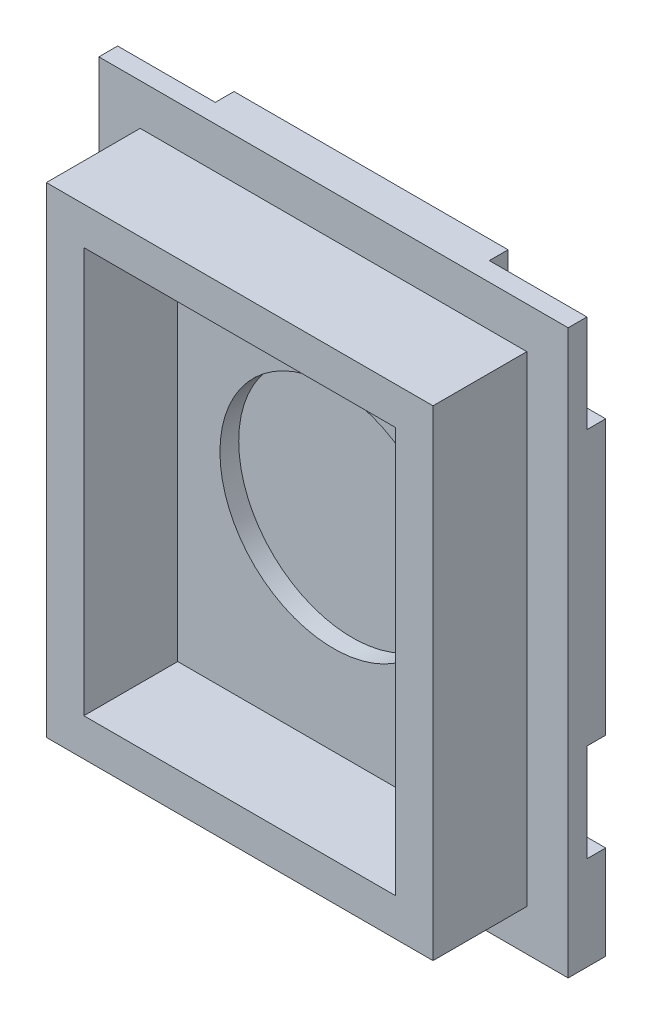
SolidWorks part; units mm, degrees
ref_plane "正面" through (0, 0, 0) normal (0, 0, 1) x (1, 0, 0)
ref_plane "平面" through (0, 0, 0) normal (0, 1, 0) x (1, 0, 0)
ref_plane "右側面" through (0, 0, 0) normal (1, 0, 0) x (0, 0, -1)
sketch "ｽｹｯﾁ1" plane through (0, 0, 0) normal (0, 0, 1) x (1, 0, 0)
  line L1 (-36.7373, 39.7071) -> (-11.7373, 39.7071)
  line L2 (-36.7373, 39.7071) -> (-36.7373, 9.7071)
  line L3 (-36.7373, 9.7071) -> (-11.7373, 9.7071)
  line L4 (-11.7373, 39.7071) -> (-11.7373, 9.7071)
  dimension "D3" = 25
  dimension "D4" = 30
extrude "ﾎﾞｽ - 押し出し1" add sketch "ｽｹｯﾁ1" along normal blind 2
sketch "ｽｹｯﾁ2" plane through (0, 0, 2) normal (0, 0, 1) x (1, 0, 0)
  line L0 (-11.7373, 39.7071) -> (-36.7373, 39.7071) construction
  line L1 (-13.9373, 37.5071) -> (-34.5373, 37.5071)
  line L2 (-13.9373, 37.5071) -> (-13.9373, 11.9071)
  line L3 (-13.9373, 11.9071) -> (-34.5373, 11.9071)
  line L4 (-34.5373, 37.5071) -> (-34.5373, 11.9071)
  line L5 (-36.7373, 9.7071) -> (-11.7373, 9.7071) construction
  line L6 (-36.7373, 39.7071) -> (-36.7373, 9.7071) construction
  line L7 (-11.7373, 9.7071) -> (-11.7373, 39.7071) construction
  dimension "D2" = 2.2
  dimension "D3" = 2.2
  dimension "D4" = 2.2
  dimension "D5" = 2.2
extrude "ﾎﾞｽ - 押し出し2" add sketch "ｽｹｯﾁ2" along normal blind 5
sketch "ｽｹｯﾁ3" plane through (0, 0, 7) normal (0, 0, 1) x (1, 0, 0)
  line L0 (-13.9373, 37.5071) -> (-34.5373, 37.5071) construction
  line L1 (-32.5373, 13.9071) -> (-15.9373, 13.9071)
  line L2 (-32.5373, 13.9071) -> (-32.5373, 35.5071)
  line L3 (-32.5373, 35.5071) -> (-15.9373, 35.5071)
  line L4 (-15.9373, 13.9071) -> (-15.9373, 35.5071)
  line L5 (-34.5373, 11.9071) -> (-13.9373, 11.9071) construction
  line L6 (-13.9373, 11.9071) -> (-13.9373, 37.5071) construction
  line L7 (-34.5373, 37.5071) -> (-34.5373, 11.9071) construction
  dimension "D1" = 21.6
  dimension "D2" = 16.6
  dimension "D3" = 2
  dimension "D4" = 2
  dimension "D5" = 2
  dimension "D6" = 2
extrude "ｶｯﾄ - 押し出し1" cut sketch "ｽｹｯﾁ3" against normal blind 5
sketch "ｽｹｯﾁ4" plane through (0, 0, 0) normal (0, 0, -1) x (-1, 0, 0)
  line L0 (11.7373, 39.7071) -> (36.7373, 39.7071) construction
  line L1 (11.7373, 39.7071) -> (16.9373, 39.7071)
  line L2 (11.7373, 39.7071) -> (11.7373, 34.5071)
  line L3 (11.7373, 34.5071) -> (16.9373, 34.5071)
  line L4 (16.9373, 39.7071) -> (16.9373, 34.5071)
  line L5 (36.7373, 39.7071) -> (31.5373, 39.7071)
  line L6 (36.7373, 39.7071) -> (36.7373, 34.5071)
  line L7 (36.7373, 34.5071) -> (31.5373, 34.5071)
  line L8 (31.5373, 39.7071) -> (31.5373, 34.5071)
  line L9 (36.7373, 14.7071) -> (31.5373, 14.7071)
  line L10 (36.7373, 14.7071) -> (36.7373, 19.9071)
  line L11 (36.7373, 19.9071) -> (31.5373, 19.9071)
  line L12 (31.5373, 14.7071) -> (31.5373, 19.9071)
  line L13 (11.7373, 14.7071) -> (16.9373, 14.7071)
  line L14 (11.7373, 14.7071) -> (11.7373, 19.9071)
  line L15 (11.7373, 19.9071) -> (16.9373, 19.9071)
  line L16 (16.9373, 14.7071) -> (16.9373, 19.9071)
  dimension "D1" = 5.2
  dimension "D2" = 5.2
  dimension "D3" = 5.2
  dimension "D4" = 5.2
  dimension "D5" = 5.2
  dimension "D6" = 5.2
  dimension "D7" = 5.2
  dimension "D8" = 25
  dimension "D9" = 25
extrude "ｶｯﾄ - 押し出し2" cut sketch "ｽｹｯﾁ4" against normal blind 1
sketch "ｽｹｯﾁ5" plane through (0, 0, 2) normal (0, 0, 1) x (1, 0, 0)
  line L0 (-36.7373, 39.7071) -> (-36.7373, 9.7071) construction
  line L1 (-11.7373, 39.7071) -> (-36.7373, 39.7071) construction
  circle A0 centre (-24.2373, 24.7071) radius 6.05
  dimension "D1" = 12.1
  dimension "D2" = 12.5
  dimension "D3" = 15
extrude "ｶｯﾄ - 押し出し3" cut sketch "ｽｹｯﾁ5" against normal blind 1
